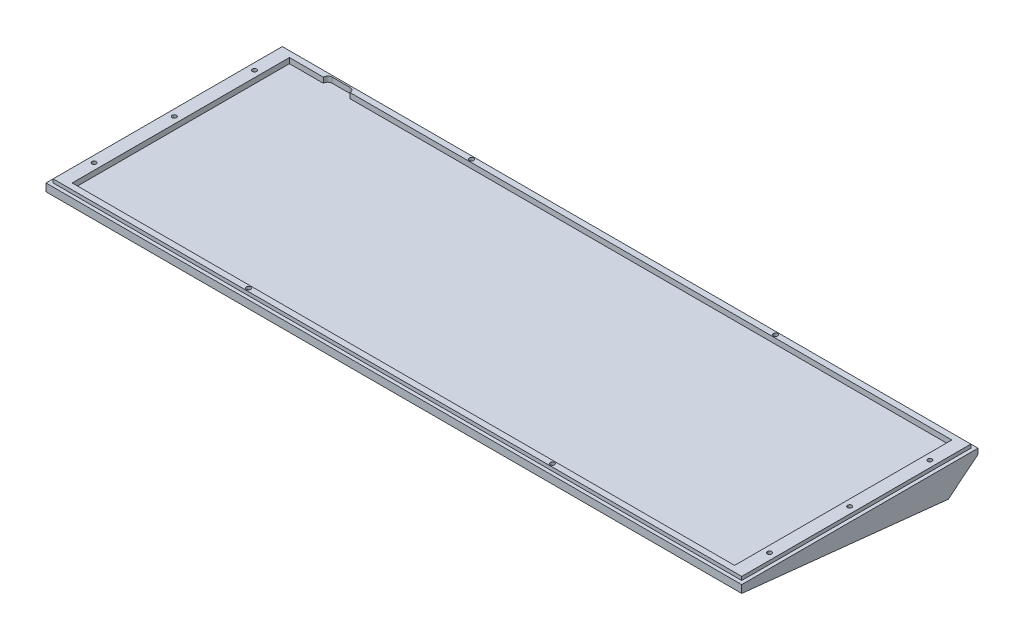
SolidWorks part; units mm, degrees
ref_plane "Front Plane" through (0, 0, 0) normal (0, 0, 1) x (1, 0, 0)
ref_plane "Top Plane" through (0, 0, 0) normal (0, 1, 0) x (1, 0, 0)
ref_plane "Right Plane" through (0, 0, 0) normal (1, 0, 0) x (0, 0, -1)
sketch "Sketch1" plane through (0, 0, 0) normal (0, 1, 0) x (1, 0, 0)
  line L1 (0, 0) -> (390.7, 0)
  line L2 (0, 0) -> (0, 132.7)
  line L3 (0, 132.7) -> (390.7, 132.7)
  line L4 (390.7, 0) -> (390.7, 132.7)
  dimension "D1" = 390.7
  dimension "D2" = 132.7
extrude "MainBody" add sketch "Sketch1" along normal blind 18.5
sketch "Sketch2" plane through (0, 18.5, 0) normal (0, 1, 0) x (1, 0, 0)
  line L0 (390.7, 132.7) -> (0, 132.7) construction
  line L1 (2, 130.7) -> (388.7, 130.7)
  line L2 (2, 130.7) -> (2, 2)
  line L3 (2, 2) -> (388.7, 2)
  line L4 (388.7, 130.7) -> (388.7, 2)
  line L5 (0, 132.7) -> (0, 0) construction
  line L7 (0, 132.7) -> (390.7, 132.7)
  line L8 (0, 132.7) -> (0, 0)
  line L9 (0, 0) -> (390.7, 0)
  line L10 (390.7, 132.7) -> (390.7, 0)
  point P4 (195.35, 130.7)
  point P7 (195.35, 132.7)
  point P8 (2, 66.35)
  point P11 (0, 66.35)
  line M5 (0, 132.7) -> (0, 0)
  line M6 (0, 0) -> (390.7, 0)
  line M7 (390.7, 0) -> (390.7, 132.7)
  line M8 (390.7, 132.7) -> (0, 132.7)
  dimension "D1" = 2
  dimension "D2" = 2
extrude "AligmentLip" cut sketch "Sketch2" against normal blind 2 contours L1 L4 L3 L2 M8 M5 M6 M7 region at (195.35, 18.5, -132.2874)
sketch "Sketch3" plane through (0, 0, 0) normal (-1, 0, 0) x (0, 0, 1)
  line L0 (-132.7, 13.5) -> (-116.0289, 0)
  line L1 (-132.7, 16.5) -> (-132.7, 0) construction
  line L2 (-132.7, 0) -> (0, 0) construction
  line L3 (-116.0289, 0) -> (0, 12.1951)
  line L4 (0, 16.5) -> (0, 0) construction
  line L5 (-132.7, 16.5) -> (0, 16.5) construction
  line L7 (-132.7, 16.5) -> (0, 16.5)
  line L8 (-132.7, 16.5) -> (-132.7, 0)
  line L9 (-132.7, 0) -> (0, 0)
  line L10 (0, 16.5) -> (0, 0)
  line M4 (-132.7, 16.5) -> (-132.7, 0)
  line M5 (-132.7, 0) -> (0, 0)
  line M6 (0, 0) -> (0, 16.5)
  dimension "D1" = 6
  dimension "D2" = 135
  dimension "D3" = 3
extrude "TypingAngle" cut sketch "Sketch3" against normal through all contours L0 M4 M5 | L3 M5 M6 region at (0, 4.5, -127.143) region at (0, 4.065, -38.6763)
sketch "Sketch4" plane through (0, 18.5, 0) normal (0, 1, 0) x (1, 0, 0)
  line L0 (2, 130.7) -> (388.7, 130.7) construction
  line L1 (9.35, 127.35) -> (381.35, 127.35)
  line L2 (9.35, 127.35) -> (9.35, 5.35)
  line L3 (9.35, 5.35) -> (381.35, 5.35)
  line L4 (381.35, 127.35) -> (381.35, 5.35)
  line L5 (2, 130.7) -> (2, 2) construction
  point P4 (195.35, 127.35)
  point P7 (195.35, 130.7)
  point P8 (9.35, 66.35)
  point P11 (2, 66.35)
  dimension "D1" = 372
  dimension "D2" = 122
extrude "PCBCutout" cut sketch "Sketch4" against normal blind 3
sketch3d "3DSketch2"
  line L1 (390.7, 0, -116.0289) -> (390.7, 12.1951, 0) construction
  line L3 (390.7, 7.5626, -100.812) -> (390.7, 1.3066, -103.5974)
  line L6 (390.7, 8.5366, -34.8083) -> (390.7, 10.4246, -37.1397)
  line L9 (390.7, 12.6516, -43.2584) -> (390.7, 13.4937, -91.502)
  arc A0 (390.7, 10.4246, -37.1397) -> (390.7, 12.6516, -43.2584) centre (390.7, 2.6531, -43.4329) cw
  arc A1 (390.7, 7.5626, -100.812) -> (390.7, 13.4937, -91.502) centre (390.7, 3.4952, -91.6766) cw
  point P10 (380.7, 2.6531, -43.4329)
  point P12 (400.7, 3.4952, -91.6766)
  dimension "D1" = 10
  dimension "D2" = 10
  dimension "D3" = 3
  dimension "D4" = 7
  dimension "D5" = 135
  dimension "D6" = 35
  dimension "D8" = 12.5
  dimension "D7" = 60
sketch "Sketch5" plane through (0, 12.0619, -1.2678) normal (0, -0.9945, 0.1045) x (1, 0, 0)
  line L0 (390.7, -33.7253) -> (388.5787, -35.8466)
  line L1 (385.7243, -41.699) -> (379.844, -89.5903)
  line L2 (384.7694, -99.4693) -> (390.7, -102.8933)
  line L3 (390.7, -115.3933) -> (390.7, 1.2747) construction
  arc A0 (388.5787, -35.8466) -> (385.7243, -41.699) centre (395.6497, -42.9177) ccw
  arc A1 (379.844, -89.5903) -> (384.7694, -99.4693) centre (389.7694, -90.809) ccw
  point P8 (0, 0)
  point P11 (0, 0)
  point P12 (0, 0)
  point P13 (0, 0)
  dimension "D3" = 10
  dimension "D4" = 10
  dimension "D1" = 7
  dimension "D2" = 3
  dimension "D5" = 60
  dimension "D6" = 45
sketch3d "3DSketch3"
  line L0 (390.7, 13.4937, -91.502) -> (379.844, 2.6971, -90.3673)
  line L1 (390.7, 12.6516, -43.2584) -> (385.7243, 7.7032, -42.7383)
loft "RightCutout" [suppressed] cut section "Sketch5" section "3DSketch2"
sketch3d "Centerline" [suppressed]
  line L0 (195.35, 15.5, -127.35) -> (195.35, 18.5, -5.35) construction
  line L1 (381.35, 15.5, -127.35) -> (9.35, 15.5, -127.35) construction
  line L2 (9.35, 18.5, -5.35) -> (381.35, 18.5, -5.35) construction
ref_plane "CenterMirrorPlane" [suppressed] through (195.35, 0, 0) normal (-1, 0, 0) x (0, 0, 1)
sketch "Sketch6" plane through (0, 18.5, 0) normal (0, 1, 0) x (1, 0, 0)
  line L0 (390.7, 132.7) -> (0, 132.7) construction
  line L1 (195.35, 132.7) -> (0, 132.7)
  line L2 (195.35, 132.7) -> (195.35, 0)
  line L3 (195.35, 0) -> (0, 0)
  line L4 (0, 132.7) -> (0, 0)
extrude "HalfBodyRemove" [suppressed] cut sketch "Sketch6" against normal through all
mirror "LeftCutout" [suppressed] about plane through (195.35, 0, 0) normal (-1, 0, 0) of bodies 113
sketch "Sketch8" plane through (0, 18.5, 0) normal (0, 1, 0) x (1, 0, 0)
  line L0 (195.35, 132.7) -> (195.35, 0) construction
  line L1 (390.7, 132.7) -> (0, 132.7) construction
  line L2 (0, 0) -> (390.7, 0) construction
  line L3 (0, 66.35) -> (195.35, 66.35) construction
  line L4 (0, 132.7) -> (0, 0) construction
  line L5 (2, 130.7) -> (388.7, 130.7) construction
  line L6 (2, 2) -> (388.7, 2) construction
  line L7 (2, 130.7) -> (2, 2) construction
  point P11 (110, 129)
  point P12 (5.7, 111.35)
  point P13 (5.7, 66.35)
  point P14 (5.7, 21.35)
  point P16 (110, 3.7)
  point P17 (0, 0)
  point P18 (0, 0)
  point P19 (0, 0)
  point P22 (0, 0)
  point P24 (0, 0)
  point P27 (280.7, 3.7)
  point P28 (385, 21.35)
  point P29 (385, 66.35)
  point P30 (385, 111.35)
  point P31 (280.7, 129)
  point P32 (0, 0)
  dimension "D1" = 1.7
  dimension "D2" = 1.7
  dimension "D3" = 110
  dimension "D4" = 45
  dimension "D5" = 45
  dimension "D6" = 3.7
hole_wizard "M2 Clearance Hole2" positions "3DSketch7" profile "Sketch10" hole size "M2" standard "ANSI Metric" end condition through all
sketch3d "3DSketch7"
  point P0 (110, 18.5, -129)
  point P3 (5.7, 18.5, -111.35)
  point P6 (5.7, 18.5, -66.35)
  point P9 (5.7, 18.5, -21.35)
  point P12 (110, 18.5, -3.7)
  point P15 (280.7, 18.5, -129)
  point P18 (280.7, 18.5, -3.7)
  point P21 (385, 18.5, -21.35)
  point P24 (385, 18.5, -66.35)
  point P27 (385, 18.5, -111.35)
sketch "Sketch10" plane through (110, 18.5, -129) normal (1, 0, 0) x (0, 0, 1)
  line L0 (0, 0) -> (0, 18.5)
  line L1 (0, 18.5) -> (1.2, 18.5)
  line L2 (1.2, 18.5) -> (1.2, 0)
  line L5 (1.2, 0) -> (0, 0)
  line L11 (0, -6.35) -> (0, 107.95) construction
  dimension "Thru Hole Dia." = 2.4
  dimension "Thru Hole Depth" = 18.5
sketch "Sketch11" plane through (0, 15.5, 0) normal (0, 1, 0) x (1, 0, 0)
  line L0 (195.35, 132.7) -> (195.35, 0) construction
  line L1 (0, 0) -> (390.7, 0) construction
  circle A0 centre (110, 129) radius 2.5
  circle A1 centre (5.7, 111.35) radius 2.5
  circle A2 centre (5.7, 66.35) radius 2.5
  circle A3 centre (5.7, 21.35) radius 2.5
  circle A4 centre (110, 3.7) radius 2.5
  circle A5 centre (280.7, 3.7) radius 2.5
  circle A6 centre (385, 21.35) radius 2.5
  circle A7 centre (385, 66.35) radius 2.5
  circle A8 centre (385, 111.35) radius 2.5
  circle A9 centre (280.7, 129) radius 2.5
  point P30 (0, 0)
  dimension "D1" = 5
extrude "Cut-Extrude2" cut sketch "Sketch11" against normal through all from offset 1 offset against normal yes
sketch "Sketch12" plane through (0, 18.5, 0) normal (0, 1, 0) x (1, 0, 0)
  line L0 (381.35, 127.35) -> (9.35, 127.35) construction
  line L1 (28.4, 127.35) -> (43.4, 127.35)
  line L2 (28.4, 127.35) -> (28.4, 129.85)
  line L3 (28.4, 129.85) -> (43.4, 129.85)
  line L4 (43.4, 127.35) -> (43.4, 129.85)
  line L5 (0, 132.7) -> (0, 0) construction
  point P6 (35.9, 129.85)
  dimension "D1" = 15
  dimension "D2" = 2.5
  dimension "D3" = 35.9
extrude "Cut-Extrude3" cut sketch "Sketch12" against normal up to surface (3 mm away) up to face at (195.35, 15.5, -66.35)
fillet "Fillet1" radius 2.5 2 edges at (43.4, 17, -129.85) (28.4, 17, -129.85)
